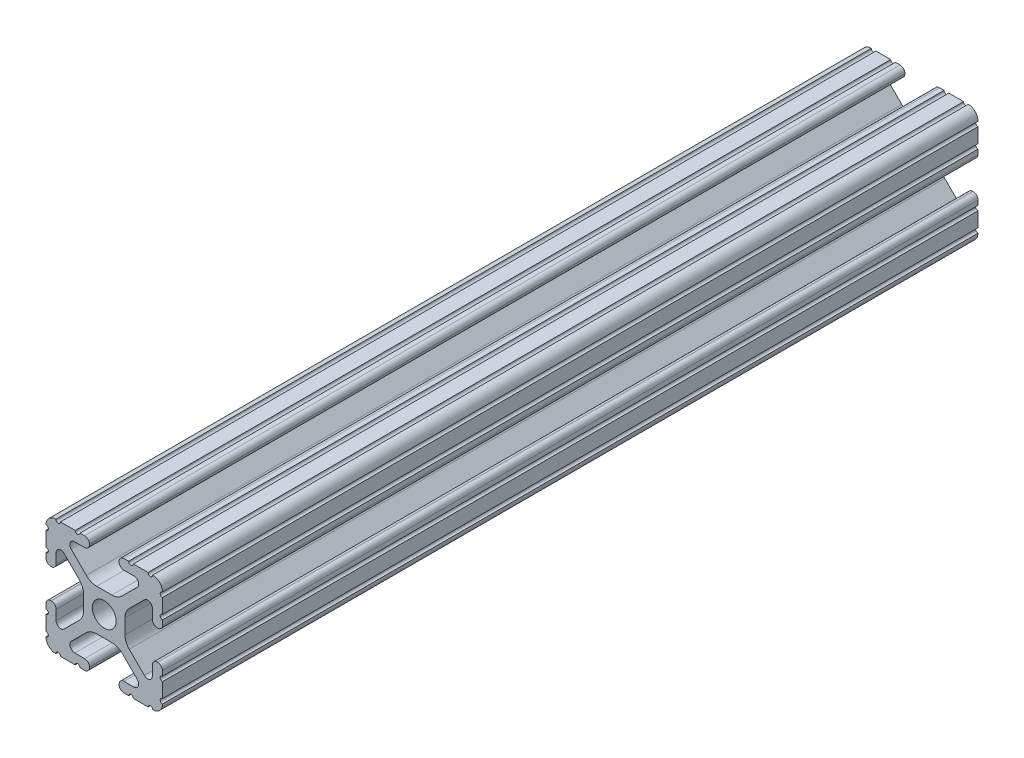
SolidWorks part; units mm, degrees
material "6061 Alloy"
ref_plane "Front Plane" through (0, 0, 0) normal (0, 0, 1) x (1, 0, 0)
ref_plane "Top Plane" through (0, 0, 0) normal (0, 1, 0) x (1, 0, 0)
ref_plane "Right Plane" through (0, 0, 0) normal (1, 0, 0) x (0, 0, -1)
sketch "Sketch1" plane through (0, 0, 0) normal (0, 0, 1) x (1, 0, 0)
  line L88 (-7.1797, -8.6452) -> (-3.9523, -5.4237)
  line L89 (-1.7093, -4.4958) -> (1.7093, -4.4958)
  line L90 (3.9523, -5.4237) -> (7.1797, -8.6452)
  line L91 (6.4164, -10.4902) -> (4.2875, -10.4902)
  line L92 (3.2385, -11.5392) -> (3.2385, -11.651)
  line L93 (4.2875, -12.7) -> (5.3171, -12.7)
  line L94 (6.3331, -12.7) -> (9.5504, -12.7)
  line L95 (12.7, -9.5504) -> (12.7, -6.3331)
  line L96 (12.7, -5.3171) -> (12.7, -4.2875)
  line L97 (11.651, -3.2385) -> (11.5392, -3.2385)
  line L98 (10.4902, -4.2875) -> (10.4902, -6.4021)
  line L99 (8.7371, -7.1294) -> (5.441, -3.8408)
  line L100 (4.5085, -1.5932) -> (4.5085, 1.5932)
  line L101 (5.441, 3.8408) -> (8.7371, 7.1294)
  line L102 (10.4902, 6.4021) -> (10.4902, 4.2875)
  line L103 (11.5392, 3.2385) -> (11.651, 3.2385)
  line L104 (12.7, 4.2875) -> (12.7, 5.3171)
  line L105 (12.7, 6.3331) -> (12.7, 9.5504)
  line L106 (9.5504, 12.7) -> (6.3331, 12.7)
  line L107 (5.3171, 12.7) -> (4.2875, 12.7)
  line L108 (3.2385, 11.651) -> (3.2385, 11.5392)
  line L109 (4.2875, 10.4902) -> (6.4768, 10.4902)
  line L110 (7.207, 8.7244) -> (3.8983, 5.4232)
  line L111 (1.6558, 4.4958) -> (-1.6558, 4.4958)
  line L112 (-3.8983, 5.4232) -> (-7.207, 8.7244)
  line L113 (-6.4768, 10.4902) -> (-4.2875, 10.4902)
  line L114 (-3.2385, 11.5392) -> (-3.2385, 11.651)
  line L115 (-4.2875, 12.7) -> (-5.3171, 12.7)
  line L116 (-6.3331, 12.7) -> (-9.5504, 12.7)
  line L117 (-12.7, 9.5504) -> (-12.7, 6.3331)
  line L118 (-12.7, 5.3171) -> (-12.7, 4.2875)
  line L119 (-11.651, 3.2385) -> (-11.5392, 3.2385)
  line L120 (-10.4902, 4.2875) -> (-10.4902, 6.4021)
  line L121 (-8.7371, 7.1294) -> (-5.441, 3.8408)
  line L122 (-4.5085, 1.5932) -> (-4.5085, -1.5932)
  line L123 (-5.441, -3.8408) -> (-8.7371, -7.1294)
  line L124 (-10.4902, -6.4021) -> (-10.4902, -4.2875)
  line L125 (-11.5392, -3.2385) -> (-11.651, -3.2385)
  line L126 (-12.7, -4.2875) -> (-12.7, -5.3171)
  line L127 (-12.7, -6.3331) -> (-12.7, -9.5504)
  line L128 (-9.5504, -12.7) -> (-6.3331, -12.7)
  line L129 (-5.3171, -12.7) -> (-4.2875, -12.7)
  line L130 (-3.2385, -11.651) -> (-3.2385, -11.5392)
  line L131 (-4.2875, -10.4902) -> (-6.4164, -10.4902)
  circle A1 centre (0, 0) radius 2.6035
  arc A104 (-7.1797, -8.6452) -> (-6.4164, -10.4902) centre (-6.4164, -9.4098) ccw
  arc A105 (-1.7093, -4.4958) -> (-3.9523, -5.4237) centre (-1.7093, -7.6708) ccw
  arc A106 (3.9523, -5.4237) -> (1.7093, -4.4958) centre (1.7093, -7.6708) ccw
  arc A107 (6.4164, -10.4902) -> (7.1797, -8.6452) centre (6.4164, -9.4098) ccw
  arc A108 (4.2875, -10.4902) -> (3.2385, -11.5392) centre (4.2875, -11.5392) ccw
  arc A109 (3.2385, -11.651) -> (4.2875, -12.7) centre (4.2875, -11.651) ccw
  arc A110 (6.3331, -12.7) -> (5.3171, -12.7) centre (5.8251, -12.7) ccw
  arc A111 (10.5664, -12.6998) -> (9.5504, -12.7) centre (10.0584, -12.7) ccw
  arc A112 (10.5664, -12.6998) -> (12.6998, -10.5664) centre (10.5918, -10.5918) ccw
  arc A113 (12.7, -9.5504) -> (12.6998, -10.5664) centre (12.7, -10.0584) ccw
  arc A114 (12.7, -5.3171) -> (12.7, -6.3331) centre (12.7, -5.8251) ccw
  arc A115 (12.7, -4.2875) -> (11.651, -3.2385) centre (11.651, -4.2875) ccw
  arc A116 (11.5392, -3.2385) -> (10.4902, -4.2875) centre (11.5392, -4.2875) ccw
  arc A117 (8.7371, -7.1294) -> (10.4902, -6.4021) centre (9.4628, -6.4021) ccw
  arc A118 (4.5085, -1.5932) -> (5.441, -3.8408) centre (7.6835, -1.5932) ccw
  arc A119 (5.441, 3.8408) -> (4.5085, 1.5932) centre (7.6835, 1.5932) ccw
  arc A120 (10.4902, 6.4021) -> (8.7371, 7.1294) centre (9.4628, 6.4021) ccw
  arc A121 (10.4902, 4.2875) -> (11.5392, 3.2385) centre (11.5392, 4.2875) ccw
  arc A122 (11.651, 3.2385) -> (12.7, 4.2875) centre (11.651, 4.2875) ccw
  arc A123 (12.7, 6.3331) -> (12.7, 5.3171) centre (12.7, 5.8251) ccw
  arc A124 (12.6998, 10.5664) -> (12.7, 9.5504) centre (12.7, 10.0584) ccw
  arc A125 (12.6998, 10.5664) -> (10.5664, 12.6998) centre (10.5918, 10.5918) ccw
  arc A126 (9.5504, 12.7) -> (10.5664, 12.6998) centre (10.0584, 12.7) ccw
  arc A127 (5.3171, 12.7) -> (6.3331, 12.7) centre (5.8251, 12.7) ccw
  arc A128 (4.2875, 12.7) -> (3.2385, 11.651) centre (4.2875, 11.651) ccw
  arc A129 (3.2385, 11.5392) -> (4.2875, 10.4902) centre (4.2875, 11.5392) ccw
  arc A130 (7.207, 8.7244) -> (6.4768, 10.4902) centre (6.4768, 9.4563) ccw
  arc A131 (1.6558, 4.4958) -> (3.8983, 5.4232) centre (1.6558, 7.6708) ccw
  arc A132 (-3.8983, 5.4232) -> (-1.6558, 4.4958) centre (-1.6558, 7.6708) ccw
  arc A133 (-6.4768, 10.4902) -> (-7.207, 8.7244) centre (-6.4768, 9.4563) ccw
  arc A134 (-4.2875, 10.4902) -> (-3.2385, 11.5392) centre (-4.2875, 11.5392) ccw
  arc A135 (-3.2385, 11.651) -> (-4.2875, 12.7) centre (-4.2875, 11.651) ccw
  arc A136 (-6.3331, 12.7) -> (-5.3171, 12.7) centre (-5.8251, 12.7) ccw
  arc A137 (-10.5664, 12.6998) -> (-9.5504, 12.7) centre (-10.0584, 12.7) ccw
  arc A138 (-10.5664, 12.6998) -> (-12.6998, 10.5664) centre (-10.5918, 10.5918) ccw
  arc A139 (-12.7, 9.5504) -> (-12.6998, 10.5664) centre (-12.7, 10.0584) ccw
  arc A140 (-12.7, 5.3171) -> (-12.7, 6.3331) centre (-12.7, 5.8251) ccw
  arc A141 (-12.7, 4.2875) -> (-11.651, 3.2385) centre (-11.651, 4.2875) ccw
  arc A142 (-11.5392, 3.2385) -> (-10.4902, 4.2875) centre (-11.5392, 4.2875) ccw
  arc A143 (-8.7371, 7.1294) -> (-10.4902, 6.4021) centre (-9.4628, 6.4021) ccw
  arc A144 (-4.5085, 1.5932) -> (-5.441, 3.8408) centre (-7.6835, 1.5932) ccw
  arc A145 (-5.441, -3.8408) -> (-4.5085, -1.5932) centre (-7.6835, -1.5932) ccw
  arc A146 (-10.4902, -6.4021) -> (-8.7371, -7.1294) centre (-9.4628, -6.4021) ccw
  arc A147 (-10.4902, -4.2875) -> (-11.5392, -3.2385) centre (-11.5392, -4.2875) ccw
  arc A148 (-11.651, -3.2385) -> (-12.7, -4.2875) centre (-11.651, -4.2875) ccw
  arc A149 (-12.7, -6.3331) -> (-12.7, -5.3171) centre (-12.7, -5.8251) ccw
  arc A150 (-12.6998, -10.5664) -> (-12.7, -9.5504) centre (-12.7, -10.0584) ccw
  arc A151 (-12.6998, -10.5664) -> (-10.5664, -12.6998) centre (-10.5918, -10.5918) ccw
  arc A152 (-9.5504, -12.7) -> (-10.5664, -12.6998) centre (-10.0584, -12.7) ccw
  arc A153 (-5.3171, -12.7) -> (-6.3331, -12.7) centre (-5.8251, -12.7) ccw
  arc A154 (-4.2875, -12.7) -> (-3.2385, -11.651) centre (-4.2875, -11.651) ccw
  arc A155 (-3.2385, -11.5392) -> (-4.2875, -10.4902) centre (-4.2875, -11.5392) ccw
extrude "Boss-Extrude1" add sketch "Sketch1" along normal mid plane 177.8
sketch "Sketch2" plane through (0, 0, 0) normal (1, 0, 0) x (0, 0, -1)
  circle A0 centre (-50.8, 0) radius 3.175
  circle A1 centre (-76.2, 0) radius 3.175
extrude "Cut-Extrude1" cut sketch "Sketch2" against normal through all both and the other way through all
sketch "Sketch3" plane through (0, 0, 0) normal (0, 1, 0) x (1, 0, 0)
  circle A0 centre (0, 76.2) radius 3.175
  circle A1 centre (0, -25.4) radius 3.175
extrude "Cut-Extrude2" cut sketch "Sketch3" against normal through all both and the other way through all
